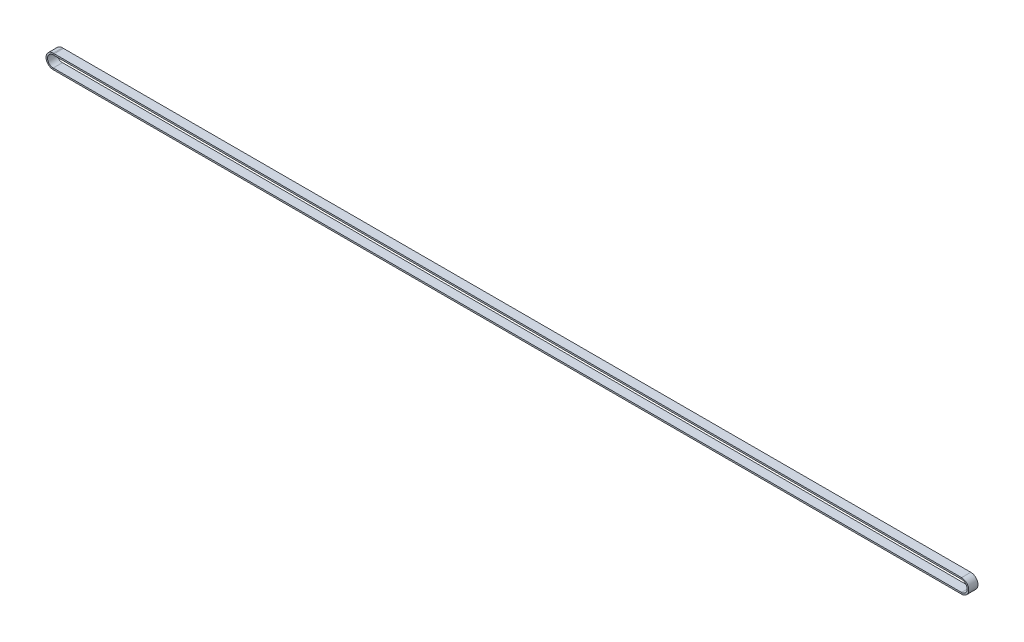
SolidWorks part; units mm, degrees
ref_plane "Front Plane" through (0, 0, 0) normal (0, 0, 1) x (1, 0, 0)
ref_plane "Top Plane" through (0, 0, 0) normal (0, 1, 0) x (1, 0, 0)
ref_plane "Right Plane" through (0, 0, 0) normal (1, 0, 0) x (0, 0, -1)
sketch "Sketch2" plane through (0, 0, 0) normal (0, 0, 1) x (1, 0, 0)
  line L0 (0, 0) -> (1, 0) construction
  line L1 (0, 0) -> (0, 1) construction
  line L2 (-1, -26.79) -> (883.5206, -26.79)
  line L3 (883.5206, -40.79) -> (-1, -40.79)
  arc A0 (-1, -40.79) -> (-1, -26.79) centre (-1, -33.79) cw
  arc A1 (883.5206, -26.79) -> (883.5206, -40.79) centre (883.5206, -33.79) cw
sketch "Sketch3" plane through (0, 0, 0) normal (1, 0, 0) x (0, 0, -1)
  line L1 (0, -28.29) -> (-9, -28.29)
  line L2 (0, -28.29) -> (0, -26.79)
  line L3 (0, -26.79) -> (-9, -26.79)
  line L4 (-9, -28.29) -> (-9, -26.79)
  dimension "D1" = 9
  dimension "D2" = 1.5
sweep "Sweep1" add profiles "Sketch3" path "Sketch2"
